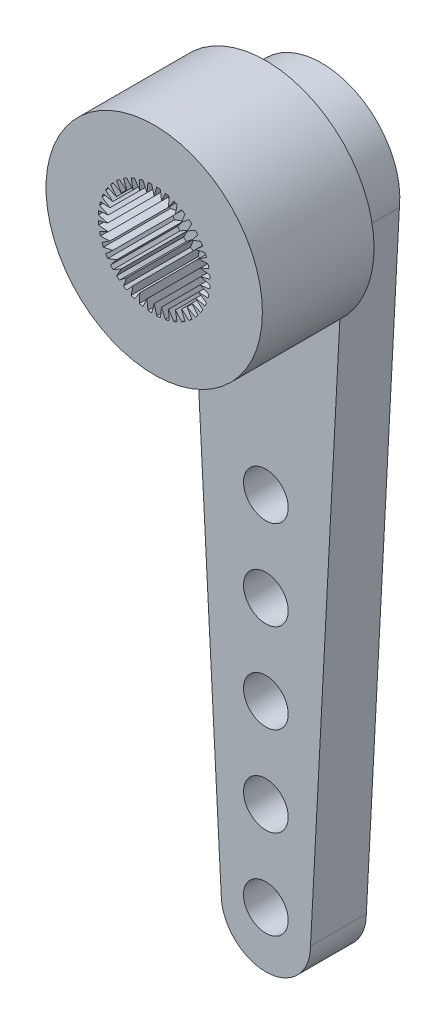
SolidWorks part; units mm, degrees
ref_plane "Front Plane" through (0, 0, 0) normal (0, 0, 1) x (1, 0, 0)
ref_plane "Top Plane" through (0, 0, 0) normal (0, 1, 0) x (1, 0, 0)
ref_plane "Right Plane" through (0, 0, 0) normal (1, 0, 0) x (0, 0, -1)
sketch "Sketch1" plane through (0, 0, 0) normal (0, 0, 1) x (1, 0, 0)
  line L0 (-2.449, 0.5022) -> (-2.0577, 0.3259)
  line L1 (-2.0577, 0.3259) -> (-2.4844, 0.2791)
  line L2 (-2.4974, 0.1129) -> (-2.0833, 0)
  line L3 (-2.0833, 0) -> (-2.4974, -0.1129)
  line L4 (-2.4844, -0.2791) -> (-2.0577, -0.3259)
  line L5 (-2.0577, -0.3259) -> (-2.449, -0.5022)
  line L6 (-2.4101, -0.6643) -> (-1.9814, -0.6438)
  line L7 (-1.9814, -0.6438) -> (-2.3403, -0.8792)
  line L8 (-2.2765, -1.0332) -> (-1.8563, -0.9458)
  line L9 (-1.8563, -0.9458) -> (-2.174, -1.2344)
  line L10 (-2.0869, -1.3766) -> (-1.6855, -1.2246)
  line L11 (-1.6855, -1.2246) -> (-1.9541, -1.5593)
  line L12 (-1.8458, -1.6861) -> (-1.4731, -1.4731)
  line L13 (-1.4731, -1.4731) -> (-1.6861, -1.8458)
  line L14 (-1.5593, -1.9541) -> (-1.2246, -1.6855)
  line L15 (-1.2246, -1.6855) -> (-1.3766, -2.0869)
  line L16 (-1.2344, -2.174) -> (-0.9458, -1.8563)
  line L17 (-0.9458, -1.8563) -> (-1.0332, -2.2765)
  line L18 (-0.8792, -2.3403) -> (-0.6438, -1.9814)
  line L19 (-0.6438, -1.9814) -> (-0.6643, -2.4101)
  line L20 (-0.5022, -2.449) -> (-0.3259, -2.0577)
  line L21 (-0.3259, -2.0577) -> (-0.2791, -2.4844)
  line L22 (-0.1129, -2.4974) -> (0, -2.0833)
  line L23 (0, -2.0833) -> (0.1129, -2.4974)
  line L24 (0.2791, -2.4844) -> (0.3259, -2.0577)
  line L25 (0.3259, -2.0577) -> (0.5022, -2.449)
  line L26 (0.6643, -2.4101) -> (0.6438, -1.9814)
  line L27 (0.6438, -1.9814) -> (0.8792, -2.3403)
  line L28 (1.0332, -2.2765) -> (0.9458, -1.8563)
  line L29 (0.9458, -1.8563) -> (1.2344, -2.174)
  line L30 (1.3766, -2.0869) -> (1.2246, -1.6855)
  line L31 (1.2246, -1.6855) -> (1.5593, -1.9541)
  line L32 (1.6861, -1.8458) -> (1.4731, -1.4731)
  line L33 (1.4731, -1.4731) -> (1.8458, -1.6861)
  line L34 (1.9541, -1.5593) -> (1.6855, -1.2246)
  line L35 (1.6855, -1.2246) -> (2.0869, -1.3766)
  line L36 (2.174, -1.2344) -> (1.8563, -0.9458)
  line L37 (1.8563, -0.9458) -> (2.2765, -1.0332)
  line L38 (2.3403, -0.8792) -> (1.9814, -0.6438)
  line L39 (1.9814, -0.6438) -> (2.4101, -0.6643)
  line L40 (2.449, -0.5022) -> (2.0577, -0.3259)
  line L41 (2.0577, -0.3259) -> (2.4844, -0.2791)
  line L42 (2.4974, -0.1129) -> (2.0833, 0)
  line L43 (2.0833, 0) -> (2.4974, 0.1129)
  line L44 (2.4844, 0.2791) -> (2.0577, 0.3259)
  line L45 (2.0577, 0.3259) -> (2.449, 0.5022)
  line L46 (2.4101, 0.6643) -> (1.9814, 0.6438)
  line L47 (1.9814, 0.6438) -> (2.3403, 0.8792)
  line L48 (2.2765, 1.0332) -> (1.8563, 0.9458)
  line L49 (1.8563, 0.9458) -> (2.174, 1.2344)
  line L50 (2.0869, 1.3766) -> (1.6855, 1.2246)
  line L51 (1.6855, 1.2246) -> (1.9541, 1.5593)
  line L52 (1.8458, 1.6861) -> (1.4731, 1.4731)
  line L53 (1.4731, 1.4731) -> (1.6861, 1.8458)
  line L54 (1.5593, 1.9541) -> (1.2246, 1.6855)
  line L55 (1.2246, 1.6855) -> (1.3766, 2.0869)
  line L56 (1.2344, 2.174) -> (0.9458, 1.8563)
  line L57 (0.9458, 1.8563) -> (1.0332, 2.2765)
  line L58 (0.8792, 2.3403) -> (0.6438, 1.9814)
  line L59 (0.6438, 1.9814) -> (0.6643, 2.4101)
  line L60 (0.5022, 2.449) -> (0.3259, 2.0577)
  line L61 (0.3259, 2.0577) -> (0.2791, 2.4844)
  line L62 (0.1129, 2.4974) -> (0, 2.0833)
  line L63 (0, 2.0833) -> (-0.1129, 2.4974)
  line L64 (-0.2791, 2.4844) -> (-0.3259, 2.0577)
  line L65 (-0.3259, 2.0577) -> (-0.5022, 2.449)
  line L66 (-0.6643, 2.4101) -> (-0.6438, 1.9814)
  line L67 (-0.6438, 1.9814) -> (-0.8792, 2.3403)
  line L68 (-1.0332, 2.2765) -> (-0.9458, 1.8563)
  line L69 (-0.9458, 1.8563) -> (-1.2344, 2.174)
  line L70 (-1.3766, 2.0869) -> (-1.2246, 1.6855)
  line L71 (-1.2246, 1.6855) -> (-1.5593, 1.9541)
  line L72 (-1.6861, 1.8458) -> (-1.4731, 1.4731)
  line L73 (-1.4731, 1.4731) -> (-1.8458, 1.6861)
  line L74 (-1.9541, 1.5593) -> (-1.6855, 1.2246)
  line L75 (-1.6855, 1.2246) -> (-2.0869, 1.3766)
  line L76 (-2.174, 1.2344) -> (-1.8563, 0.9458)
  line L77 (-1.8563, 0.9458) -> (-2.2765, 1.0332)
  line L78 (-2.3403, 0.8792) -> (-1.9814, 0.6438)
  line L79 (-1.9814, 0.6438) -> (-2.4101, 0.6643)
  arc A0 (-2.4844, 0.2791) -> (-2.4974, 0.1129) centre (0, 0) ccw
  arc A1 (-2.4974, -0.1129) -> (-2.4844, -0.2791) centre (0, 0) ccw
  arc A2 (-2.449, -0.5022) -> (-2.4101, -0.6643) centre (0, 0) ccw
  arc A3 (-2.3403, -0.8792) -> (-2.2765, -1.0332) centre (0, 0) ccw
  arc A4 (-2.174, -1.2344) -> (-2.0869, -1.3766) centre (0, 0) ccw
  arc A5 (-1.9541, -1.5593) -> (-1.8458, -1.6861) centre (0, 0) ccw
  arc A6 (-1.6861, -1.8458) -> (-1.5593, -1.9541) centre (0, 0) ccw
  arc A7 (-1.3766, -2.0869) -> (-1.2344, -2.174) centre (0, 0) ccw
  arc A8 (-1.0332, -2.2765) -> (-0.8792, -2.3403) centre (0, 0) ccw
  arc A9 (-0.6643, -2.4101) -> (-0.5022, -2.449) centre (0, 0) ccw
  arc A10 (-0.2791, -2.4844) -> (-0.1129, -2.4974) centre (0, 0) ccw
  arc A11 (0.1129, -2.4974) -> (0.2791, -2.4844) centre (0, 0) ccw
  arc A12 (0.5022, -2.449) -> (0.6643, -2.4101) centre (0, 0) ccw
  arc A13 (0.8792, -2.3403) -> (1.0332, -2.2765) centre (0, 0) ccw
  arc A14 (1.2344, -2.174) -> (1.3766, -2.0869) centre (0, 0) ccw
  arc A15 (1.5593, -1.9541) -> (1.6861, -1.8458) centre (0, 0) ccw
  arc A16 (1.8458, -1.6861) -> (1.9541, -1.5593) centre (0, 0) ccw
  arc A17 (2.0869, -1.3766) -> (2.174, -1.2344) centre (0, 0) ccw
  arc A18 (2.2765, -1.0332) -> (2.3403, -0.8792) centre (0, 0) ccw
  arc A19 (2.4101, -0.6643) -> (2.449, -0.5022) centre (0, 0) ccw
  arc A20 (2.4844, -0.2791) -> (2.4974, -0.1129) centre (0, 0) ccw
  arc A21 (2.4974, 0.1129) -> (2.4844, 0.2791) centre (0, 0) ccw
  arc A22 (2.449, 0.5022) -> (2.4101, 0.6643) centre (0, 0) ccw
  arc A23 (2.3403, 0.8792) -> (2.2765, 1.0332) centre (0, 0) ccw
  arc A24 (2.174, 1.2344) -> (2.0869, 1.3766) centre (0, 0) ccw
  arc A25 (1.9541, 1.5593) -> (1.8458, 1.6861) centre (0, 0) ccw
  arc A26 (1.6861, 1.8458) -> (1.5593, 1.9541) centre (0, 0) ccw
  arc A27 (1.3766, 2.0869) -> (1.2344, 2.174) centre (0, 0) ccw
  arc A28 (1.0332, 2.2765) -> (0.8792, 2.3403) centre (0, 0) ccw
  arc A29 (0.6643, 2.4101) -> (0.5022, 2.449) centre (0, 0) ccw
  arc A30 (0.2791, 2.4844) -> (0.1129, 2.4974) centre (0, 0) ccw
  arc A31 (-0.1129, 2.4974) -> (-0.2791, 2.4844) centre (0, 0) ccw
  arc A32 (-0.5022, 2.449) -> (-0.6643, 2.4101) centre (0, 0) ccw
  arc A33 (-0.8792, 2.3403) -> (-1.0332, 2.2765) centre (0, 0) ccw
  arc A34 (-1.2344, 2.174) -> (-1.3766, 2.0869) centre (0, 0) ccw
  arc A35 (-1.5593, 1.9541) -> (-1.6861, 1.8458) centre (0, 0) ccw
  arc A36 (-1.8458, 1.6861) -> (-1.9541, 1.5593) centre (0, 0) ccw
  arc A37 (-2.0869, 1.3766) -> (-2.174, 1.2344) centre (0, 0) ccw
  arc A38 (-2.2765, 1.0332) -> (-2.3403, 0.8792) centre (0, 0) ccw
  arc A39 (-2.4101, 0.6643) -> (-2.449, 0.5022) centre (0, 0) ccw
  circle A40 centre (0, 0) radius 2.5
  dimension "D1" = 5
sketch "Sketch2" plane through (0, 0, 0) normal (0, 0, 1) x (1, 0, 0)
  line L0 (-12.25, 0) -> (12.25, 0) construction
  line L1 (0, 12.25) -> (0, -12.25) construction
  circle A0 centre (0, 0) radius 12.25
  circle A2 centre (0, 8.25) radius 1.5944
  circle A3 centre (0, -8.25) radius 1.5944
  circle A4 centre (-8.25, 0) radius 1.5944
  circle A5 centre (8.25, 0) radius 1.5944
  dimension "D1" = 16.5
  dimension "D2" = 24.5
  dimension "D3" = 16.5
  dimension "D4" = 8.25
  dimension "D5" = 8.25
extrude "Boss-Extrude1" add sketch "Sketch2" along normal blind 2
sketch "Sketch3" plane through (0, 0, 2) normal (0, 0, 1) x (1, 0, 0)
  circle A0 centre (0, 0) radius 1.5
extrude "Cut-Extrude1" cut sketch "Sketch3" against normal blind 2
sketch "Sketch4" plane through (0, 0, 2) normal (0, 0, 1) x (1, 0, 0)
  circle A0 centre (0, 0) radius 2.5
  circle A1 centre (0, 0) radius 3.25
  dimension "D1" = 5
  dimension "D2" = 6.5
extrude "Boss-Extrude2" add sketch "Sketch4" along normal blind 3
extrude "Boss-Extrude3" add sketch "Sketch1" along normal blind 3 from surface contours L2 A40 L3 | L0 A40 L1 | L78 A40 L79 | L76 A40 L77 | L74 A40 L75 | L72 A40 L73 | L70 A40 L71 | L68 A40 L69 | L66 A40 L67 | L64 A40 L65 | L62 A40 L63 | L60 A40 L61 | L58 A40 L59 | L56 A40 L57 | L54 A40 L55 | L52 A40 L53 | L50 A40 L51 | L48 A40 L49 | L46 A40 L47 | L44 A40 L45 | L42 A40 L43 | L40 A40 L41 | L38 A40 L39 | L36 A40 L37 | L34 A40 L35 | L32 A40 L33 | L30 A40 L31 | L28 A40 L29 | L26 A40 L27 | L24 A40 L25 | L22 A40 L23 | L20 A40 L21 | L18 A40 L19 | L16 A40 L17 | L14 A40 L15 | L12 A40 L13 | L10 A40 L11 | L8 A40 L9 | L6 A40 L7 | L4 A40 L5 region at (-2.3315, 0.3693, 0) region at (-2.245, 0.7294, 0) region at (-2.3605, 0, 0) region at (-2.1033, 1.0717, 0) region at (-2.3315, -0.3693, 0) region at (-1.9097, 1.3875, 0) region at (-2.245, -0.7294, 0) region at (-1.6692, 1.6692, 0) region at (-2.1033, -1.0717, 0) region at (-1.3875, 1.9097, 0) region at (-1.9097, -1.3875, 0) region at (-1.0717, 2.1033, 0) region at (-1.6692, -1.6692, 0) region at (-0.7294, 2.245, 0) region at (-1.3875, -1.9097, 0) region at (-0.3693, 2.3315, 0) region at (-1.0717, -2.1033, 0) region at (0, 2.3605, 0) region at (-0.7294, -2.245, 0) region at (0.3693, 2.3315, 0) region at (-0.3693, -2.3315, 0) region at (0.7294, 2.245, 0) region at (0, -2.3605, 0) region at (1.0717, 2.1033, 0) region at (0.3693, -2.3315, 0) region at (1.3875, 1.9097, 0) region at (0.7294, -2.245, 0) region at (1.6692, 1.6692, 0) region at (1.0717, -2.1033, 0) region at (1.9097, 1.3875, 0) region at (1.3875, -1.9097, 0) region at (2.1033, 1.0717, 0) region at (1.6692, -1.6692, 0) region at (2.245, 0.7294, 0) region at (1.9097, -1.3875, 0) region at (2.3315, 0.3693, 0) region at (2.1033, -1.0717, 0) region at (2.3605, 0, 0) region at (2.245, -0.7294, 0) region at (2.3315, -0.3693, 0) starting at face at (1.5, 0, 2)
sketch "Sketch5" plane through (0, 0, 0) normal (0, 0, -1) x (-1, 0, 0)
  circle A0 centre (0, 0) radius 2.5
  point P4 (0, 0)
  dimension "D1" = 5
extrude "Cut-Extrude2" cut sketch "Sketch5" against normal blind 0.5
sketch "Sketch6" plane through (0, 0, 2) normal (0, 0, 1) x (1, 0, 0)
  circle A0 centre (0, 0) radius 4.8448
  circle A1 centre (0, 0) radius 12.25
  dimension "D1" = 9.6895
extrude "Cut-Extrude3" cut sketch "Sketch6" against normal blind 10
sketch "Sketch7" plane through (0, 0, 2) normal (0, 0, 1) x (1, 0, 0)
  circle A1 centre (0, 0) radius 4.8448
  circle A3 centre (0, 0) radius 4.8448
  circle M2 centre (0, 0) radius 3.25
  circle M3 centre (0, 0) radius 4.8448
  dimension "D2" = 9.6895
  dimension "D1" = 0
extrude "Boss-Extrude5" add sketch "Sketch7" along normal up to surface (3 mm away) contours M3 M2 region at (-4.7077, 0, 2) up to face at (3.25, 0, 5)
sketch "Sketch8" plane through (0, 0, 0) normal (0, 0, -1) x (-1, 0, 0)
  circle A0 centre (0, 0) radius 4.8448 construction
  circle A1 centre (0, 0) radius 4.8448
  circle A2 centre (0, 0) radius 3.5
  dimension "D1" = 7
extrude "Boss-Extrude6" add sketch "Sketch8" against normal up to surface (5 mm away) up to face at (0, 0, 5)
sketch "Sketch9" plane through (0, 0, 0) normal (0, 0, -1) x (-1, 0, 0)
  circle A0 centre (0, 0) radius 2.5
  circle A1 centre (0, 0) radius 3.5
  dimension "D1" = 5
  dimension "D2" = 7
extrude "Boss-Extrude7" add sketch "Sketch9" along normal blind 2.5
sketch "Sketch11" plane through (0, 0, -2.5) normal (0, 0, -1) x (-1, 0, 0)
  line L0 (0, 0) -> (0, -28.5) construction
  line L1 (-3.5, 0) -> (-2, -28.5)
  line L2 (3.5, 0) -> (2, -28.5)
  line L3 (0, 3.5) -> (0, -30.5) construction
  arc A1 (-2, -28.5) -> (2, -28.5) centre (0, -28.5) ccw
  circle A2 centre (0, 0) radius 3.5 construction
  arc A3 (-3.5, 0) -> (3.5, 0) centre (0, 0) ccw
  circle A5 centre (0, -16) radius 1
  circle A6 centre (0, -12) radius 1
  circle A7 centre (0, -20) radius 1
  circle A8 centre (0, -24) radius 1
  circle A9 centre (0, -28) radius 1
  point P1 (0, -30.5)
  point P3 (0, 3.5)
  circle M4 centre (0, 0) radius 3.5
  dimension "D1" = 2
  dimension "D2" = 34
  dimension "D3" = 20
  dimension "D6" = 2
  dimension "D7" = 2
  dimension "D8" = 2
  dimension "D9" = 2
  dimension "D10" = 2
  dimension "D4" = 16
  dimension "D5" = 12
  dimension "D11" = 24
  dimension "D12" = 28
extrude "Boss-Extrude8" add sketch "Sketch11" against normal blind 2.5 contours L1 A1 L2 A7 A6 A5 M4 region at (0, -14.6175, -2.5)
ref_axis "ServoAxis" through (0, 0, 0.5) along (0, 0, 1)
sketch "Sketch13" plane through (-3.4903, -0.1837, 0) normal (-0.9986, -0.0526, 0) x (0, 0, 1)
  line L0 (0, -4.8448) -> (5, -4.8448) construction
  line L1 (0, 4.8448) -> (6, 4.8448)
  line L2 (0, 4.8448) -> (0, -4.8448)
  line L3 (0, -4.8448) -> (6, -4.8448)
  line L4 (6, 4.8448) -> (6, -4.8448)
  line L6 (3.5, -4.1666) -> (6.4262, -4.1666)
  line L7 (3.5, -4.1666) -> (3.5, 4.0973)
  line L8 (3.5, 4.0973) -> (6.4262, 4.0973)
  line L9 (6.4262, -4.1666) -> (6.4262, 4.0973)
  dimension "D1" = 6
extrude "Cut-Extrude4" cut sketch "Sketch13" against normal blind 30.2 contours L6 L9 L8 L7 L4 rebuild error yes
